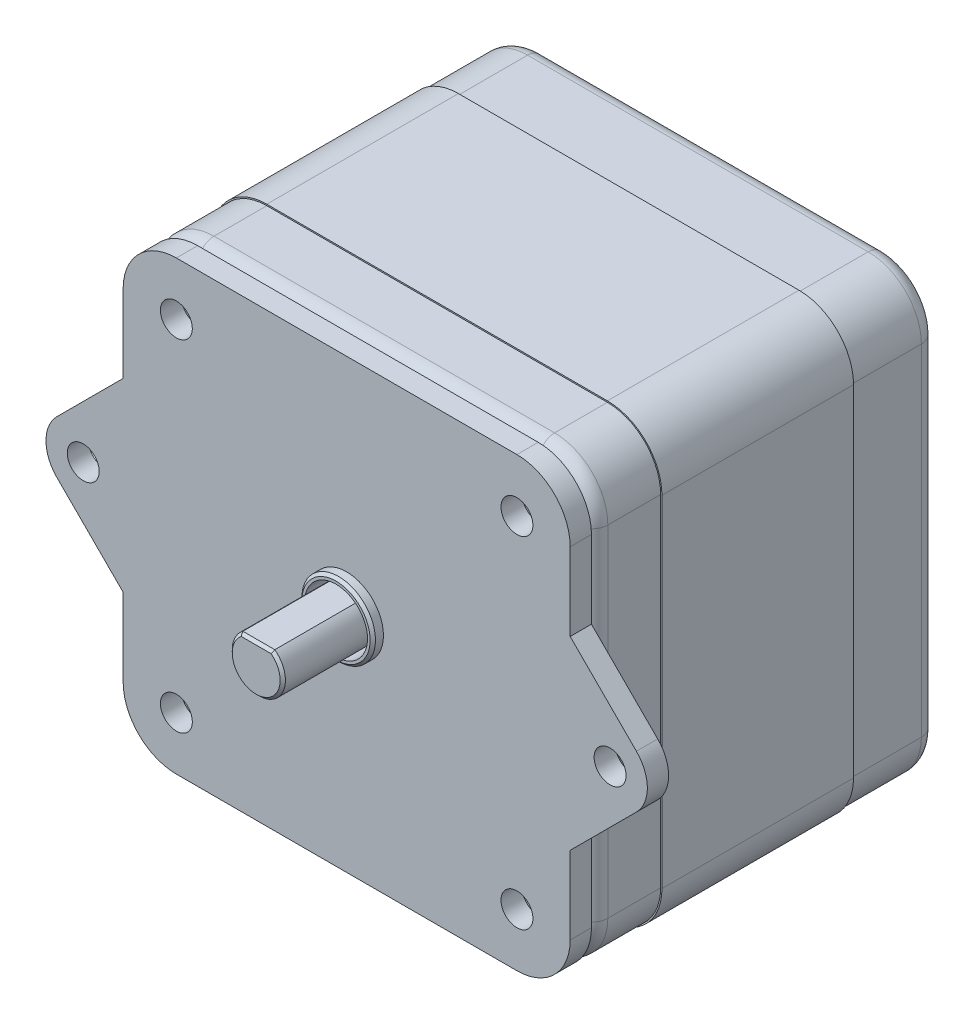
SolidWorks part; units mm, degrees
ref_plane "Front Plane" through (0, 0, 0) normal (0, 0, 1) x (1, 0, 0)
ref_plane "Top Plane" through (0, 0, 0) normal (0, 1, 0) x (1, 0, 0)
ref_plane "Right Plane" through (0, 0, 0) normal (1, 0, 0) x (0, 0, -1)
sketch "Sketch1" plane through (0, 0, 0) normal (0, 0, 1) x (1, 0, 0)
  line L0 (-27.2249, 2.4749) -> (-21, 8.6997)
  line L1 (-16, 21) -> (16, 21)
  line L2 (-21, 16) -> (-21, 8.6997)
  line L3 (-16, -21) -> (16, -21)
  line L4 (21, 16) -> (21, 8.6997)
  line L5 (-21, 21) -> (21, -21) construction
  line L6 (-21, -21) -> (21, 21) construction
  line L7 (-27.2249, -2.4749) -> (-21, -8.6997)
  line L8 (0, 14.4515) -> (0, -6.8676) construction
  line L9 (27.2249, -2.4749) -> (21, -8.6997)
  line L10 (27.2249, 2.4749) -> (21, 8.6997)
  line L11 (-21, -8.6997) -> (-21, -16)
  line L12 (21, -8.6997) -> (21, -16)
  arc A0 (-21, -16) -> (-16, -21) centre (-16, -16) ccw
  arc A1 (16, -21) -> (21, -16) centre (16, -16) ccw
  arc A2 (16, 21) -> (21, 16) centre (16, 16) cw
  arc A3 (-16, 21) -> (-21, 16) centre (-16, 16) ccw
  circle A4 centre (-24.75, 0) radius 1.5
  circle A5 centre (24.75, 0) radius 1.5
  arc A6 (27.2249, -2.4749) -> (27.2249, 2.4749) centre (24.75, 0) ccw
  arc A7 (-27.2249, 2.4749) -> (-27.2249, -2.4749) centre (-24.75, 0) ccw
  circle A8 centre (24.75, 0) radius 3.5 construction
  circle A9 centre (-24.75, 0) radius 3.5 construction
  point P0 (0, 0)
  dimension "D3" = 5
  dimension "D4" = 3
  dimension "D5" = 42
  dimension "D7" = 2
  dimension "D8" = 3
  dimension "D11" = 2
  dimension "D12" = 24.75
  dimension "D2" = 42
  dimension "D6" = 24.75
  dimension "D9" = 135
  dimension "D10" = 45
  dimension "D13" = 135
sketch "Sketch2" plane through (0, 0, 0) normal (0, 0, 1) x (1, 0, 0)
  line L0 (-21, 16) -> (-21, 8.6997) construction
  line L4 (-16, -21) -> (16, -21) construction
  line L8 (21, 16) -> (21, 8.6997) construction
  line L9 (-16, 21) -> (16, 21) construction
  line L10 (-21, 16) -> (-21, -16)
  line L14 (-16, -21) -> (16, -21)
  line L18 (21, 16) -> (21, -16)
  line L19 (-16, 21) -> (16, 21)
  arc A1 (-21, -16) -> (-16, -21) centre (-16, -16) ccw construction
  arc A2 (16, -21) -> (21, -16) centre (16, -16) ccw construction
  arc A4 (21, 16) -> (16, 21) centre (16, 16) ccw construction
  arc A5 (-16, 21) -> (-21, 16) centre (-16, 16) ccw construction
  arc A7 (-21, -16) -> (-16, -21) centre (-16, -16) ccw
  arc A8 (16, -21) -> (21, -16) centre (16, -16) ccw
  arc A10 (21, 16) -> (16, 21) centre (16, 16) ccw
  arc A11 (-16, 21) -> (-21, 16) centre (-16, 16) ccw
extrude "Boss-Extrude1" add sketch "Sketch2" against normal blind 34.5
sketch "Sketch3" plane through (0, 0, 0) normal (0, 0, 1) x (1, 0, 0)
  line L0 (-27.2249, 2.4749) -> (-21, 8.6997) construction
  line L1 (-21, 16) -> (-21, 8.6997) construction
  line L2 (-16, 21) -> (16, 21) construction
  line L3 (21, 16) -> (21, 8.6997) construction
  line L4 (27.2249, 2.4749) -> (21, 8.6997) construction
  line L5 (27.2249, -2.4749) -> (21, -8.6997) construction
  line L6 (21, -8.6997) -> (21, -16) construction
  line L7 (-16, -21) -> (16, -21) construction
  line L8 (-21, -8.6997) -> (-21, -16) construction
  line L9 (-27.2249, -2.4749) -> (-21, -8.6997) construction
  line L10 (-27.2249, 2.4749) -> (-21, 8.6997)
  line L11 (-21, 16) -> (-21, 8.6997)
  line L12 (-16, 21) -> (16, 21)
  line L13 (21, 16) -> (21, 8.6997)
  line L14 (27.2249, 2.4749) -> (21, 8.6997)
  line L15 (27.2249, -2.4749) -> (21, -8.6997)
  line L16 (21, -8.6997) -> (21, -16)
  line L17 (-16, -21) -> (16, -21)
  line L18 (-21, -8.6997) -> (-21, -16)
  line L19 (-27.2249, -2.4749) -> (-21, -8.6997)
  arc A0 (-16, 21) -> (-21, 16) centre (-16, 16) ccw construction
  arc A1 (21, 16) -> (16, 21) centre (16, 16) ccw construction
  arc A2 (27.2249, -2.4749) -> (27.2249, 2.4749) centre (24.75, 0) ccw construction
  arc A3 (16, -21) -> (21, -16) centre (16, -16) ccw construction
  arc A4 (-21, -16) -> (-16, -21) centre (-16, -16) ccw construction
  arc A5 (-27.2249, 2.4749) -> (-27.2249, -2.4749) centre (-24.75, 0) ccw construction
  circle A6 centre (-24.75, 0) radius 1.5 construction
  circle A7 centre (24.75, 0) radius 1.5 construction
  arc A8 (-16, 21) -> (-21, 16) centre (-16, 16) ccw
  arc A9 (21, 16) -> (16, 21) centre (16, 16) ccw
  arc A10 (27.2249, -2.4749) -> (27.2249, 2.4749) centre (24.75, 0) ccw
  arc A11 (16, -21) -> (21, -16) centre (16, -16) ccw
  arc A12 (-21, -16) -> (-16, -21) centre (-16, -16) ccw
  arc A13 (-27.2249, 2.4749) -> (-27.2249, -2.4749) centre (-24.75, 0) ccw
  circle A14 centre (-24.75, 0) radius 1.5
  circle A15 centre (24.75, 0) radius 1.5
extrude "Boss-Extrude2" add sketch "Sketch3" against normal blind 2
sketch "Sketch4" plane through (0, 0, 0) normal (0, 0, 1) x (1, 0, 0)
  line L0 (-1.5, 2) -> (1.5, 2)
  arc A0 (-1.5, 2) -> (1.5, 2) centre (0, 0) ccw
  dimension "D1" = 5
  dimension "D2" = 2
extrude "Boss-Extrude3" add sketch "Sketch4" along normal blind 8.5
sketch "Sketch5" plane through (0, 0, 0) normal (0, 0, 1) x (1, 0, 0)
  circle A0 centre (0, 0) radius 3.4575
  circle A1 centre (0, 0) radius 2.9575
  dimension "D1" = 0.5
extrude "Boss-Extrude4" add sketch "Sketch5" along normal blind 1
sketch "Sketch6" plane through (0, 0, 0) normal (0, 0, 1) x (1, 0, 0)
  line L1 (1.5, 2) -> (-1.5, 2)
  line L2 (1.5, 2) -> (-1.5, 2)
  circle A1 centre (0, 0) radius 2.9575
  circle A2 centre (0, 0) radius 2.9575
  arc A3 (-1.5, 2) -> (1.5, 2) centre (0, 0) ccw
  arc A4 (-1.5, 2) -> (1.5, 2) centre (0, 0) ccw
  dimension "D1" = 0
  dimension "D2" = 0
extrude "Cut-Extrude1" cut sketch "Sketch6" against normal blind 10
chamfer "Chamfer1" distance 0.25 angle 45 3 edges at (0, 2, 8.5) (0, -2.5, 8.5) (3.4575, 0, 1)
sketch "Sketch7" plane through (0, 0, -2) normal (0, 0, -1) x (-1, 0, 0)
  line L0 (-16, 21) -> (16, 21) construction
  line L1 (21, 16) -> (21, 8.6997) construction
  line L2 (-21, 8.6997) -> (-21, 16) construction
  line L3 (16, -21) -> (-16, -21) construction
  line L4 (-16, 21) -> (16, 21)
  line L5 (21, 16) -> (21, -16)
  line L6 (-21, -16) -> (-21, 16)
  line L7 (16, -21) -> (-16, -21)
  line L8 (-16, 20) -> (16, 20)
  line L9 (20, 16) -> (20, -16)
  line L10 (16, -20) -> (-16, -20)
  line L11 (-20, -16) -> (-20, 16)
  arc A0 (21, 16) -> (16, 21) centre (16, 16) ccw construction
  arc A1 (-16, 21) -> (-21, 16) centre (-16, 16) ccw construction
  arc A2 (-21, -16) -> (-16, -21) centre (-16, -16) ccw construction
  arc A3 (16, -21) -> (21, -16) centre (16, -16) ccw construction
  arc A4 (21, 16) -> (16, 21) centre (16, 16) ccw
  arc A5 (-16, 21) -> (-21, 16) centre (-16, 16) ccw
  arc A6 (-21, -16) -> (-16, -21) centre (-16, -16) ccw
  arc A7 (16, -21) -> (21, -16) centre (16, -16) ccw
  arc A8 (20, 16) -> (16, 20) centre (16, 16) ccw
  arc A9 (16, -20) -> (20, -16) centre (16, -16) ccw
  arc A10 (-20, -16) -> (-16, -20) centre (-16, -16) ccw
  arc A11 (-16, 20) -> (-20, 16) centre (-16, 16) ccw
  dimension "D1" = 1
extrude "Cut-Extrude2" cut sketch "Sketch7" along normal blind 0.125
fillet "Fillet1" radius 1.5 16 edges at (19.5355, 19.5355, -34.5) (21, 0, -34.5) (19.5355, -19.5355, -34.5) (0, -21, -34.5) (-19.5355, -19.5355, -34.5) (-21, 0, -34.5) (-19.5355, 19.5355, -34.5) (0, 21, -34.5) (-19.5355, 19.5355, -2.125) (-21, 0, -2.125) (-19.5355, -19.5355, -2.125) (0, -21, -2.125) (19.5355, -19.5355, -2.125) (21, 0, -2.125) (19.5355, 19.5355, -2.125) (0, 21, -2.125)
sketch "Sketch8" plane through (0, 0, 0) normal (0, 0, 1) x (1, 0, 0)
  line L0 (16, 21) -> (-16, 21) construction
  line L1 (-21, 16) -> (-21, 8.6997) construction
  line L2 (0, 8.3299) -> (0, 0) construction
  line L3 (0, 0) -> (7.0393, 0) construction
  circle A0 centre (-16, 16) radius 1.5
  circle A1 centre (16, 16) radius 1.5
  circle A2 centre (16, -16) radius 1.5
  circle A3 centre (-16, -16) radius 1.5
  dimension "D1" = 3
  dimension "D2" = 5
  dimension "D3" = 5
extrude "Cut-Extrude3" cut sketch "Sketch8" against normal up to vertex (2 mm away) up to point (-21, 8.6997, -2)
sketch "Sketch9" plane through (0, 0, -34.5) normal (0, 0, -1) x (-1, 0, 0)
  circle A0 centre (-16, 16) radius 1.5 construction
  circle A1 centre (16, 16) radius 1.5 construction
  circle A2 centre (16, -16) radius 1.5 construction
  circle A3 centre (-16, -16) radius 1.5 construction
  circle A4 centre (-16, 16) radius 1.5 construction
  circle A5 centre (16, 16) radius 1.5 construction
  circle A6 centre (16, -16) radius 1.5 construction
  circle A7 centre (-16, -16) radius 1.5 construction
  circle A8 centre (0, 0) radius 2.9575 construction
  circle A9 centre (0, 0) radius 2.9575
  circle A14 centre (-16, 16) radius 2.75
  circle A15 centre (16, 16) radius 2.75
  circle A16 centre (16, -16) radius 2.75
  circle A17 centre (-16, -16) radius 2.75
  dimension "D1" = 1.25
extrude "Boss-Extrude5" add sketch "Sketch9" along normal blind 0.5
sketch "Sketch10" plane through (0, 0, -35) normal (0, 0, -1) x (-1, 0, 0)
  line L0 (-17.5, 16) -> (-14.5, 16) construction
  line L1 (-16, 14.5) -> (-16, 17.5) construction
  line L2 (-15.5, 14.5) -> (-15.5, 15.5)
  line L3 (-17.5, 15.5) -> (-16.5, 15.5)
  line L4 (-16.5, 14.5) -> (-16.5, 15.5)
  line L5 (-17.5, 16.5) -> (-16.5, 16.5)
  line L6 (-16.5, 17.5) -> (-15.5, 17.5)
  line L7 (-14.5, 16.5) -> (-14.5, 15.5)
  line L8 (-15.5, 14.5) -> (-16.5, 14.5)
  line L9 (-17.5, 15.5) -> (-17.5, 16.5)
  line L10 (-15.5, 16.5) -> (-14.5, 16.5)
  line L11 (-17.5, 16.5) -> (-14.5, 16.5) construction
  line L12 (-16.5, 16.5) -> (-16.5, 17.5)
  line L13 (-16.5, 14.5) -> (-16.5, 17.5) construction
  line L14 (-15.5, 15.5) -> (-14.5, 15.5)
  line L15 (-17.5, 15.5) -> (-14.5, 15.5) construction
  line L16 (-15.5, 16.5) -> (-15.5, 17.5)
  line L17 (-15.5, 14.5) -> (-15.5, 17.5) construction
  line L18 (0, 5.9902) -> (0, 0) construction
  line L19 (0, 0) -> (6.6801, 0) construction
  line L20 (16, 14.5) -> (16, 17.5) construction
  line L21 (17.5, 16) -> (14.5, 16) construction
  line L22 (15.5, 16.5) -> (15.5, 17.5)
  line L23 (15.5, 15.5) -> (14.5, 15.5)
  line L24 (16.5, 16.5) -> (16.5, 17.5)
  line L25 (15.5, 16.5) -> (14.5, 16.5)
  line L26 (17.5, 15.5) -> (17.5, 16.5)
  line L27 (15.5, 14.5) -> (16.5, 14.5)
  line L28 (14.5, 16.5) -> (14.5, 15.5)
  line L29 (16.5, 17.5) -> (15.5, 17.5)
  line L30 (17.5, 16.5) -> (16.5, 16.5)
  line L31 (16.5, 14.5) -> (16.5, 15.5)
  line L32 (17.5, 15.5) -> (16.5, 15.5)
  line L33 (15.5, 14.5) -> (15.5, 15.5)
  line L34 (17.5, -16) -> (14.5, -16) construction
  line L35 (16, -14.5) -> (16, -17.5) construction
  line L36 (-16, -14.5) -> (-16, -17.5) construction
  line L37 (-17.5, -16) -> (-14.5, -16) construction
  line L38 (15.5, -14.5) -> (15.5, -15.5)
  line L39 (17.5, -15.5) -> (16.5, -15.5)
  line L40 (16.5, -14.5) -> (16.5, -15.5)
  line L41 (17.5, -16.5) -> (16.5, -16.5)
  line L42 (16.5, -17.5) -> (15.5, -17.5)
  line L43 (14.5, -16.5) -> (14.5, -15.5)
  line L44 (15.5, -14.5) -> (16.5, -14.5)
  line L45 (17.5, -15.5) -> (17.5, -16.5)
  line L46 (15.5, -16.5) -> (14.5, -16.5)
  line L47 (16.5, -16.5) -> (16.5, -17.5)
  line L48 (15.5, -15.5) -> (14.5, -15.5)
  line L49 (15.5, -16.5) -> (15.5, -17.5)
  line L50 (-15.5, -16.5) -> (-15.5, -17.5)
  line L51 (-15.5, -15.5) -> (-14.5, -15.5)
  line L52 (-16.5, -16.5) -> (-16.5, -17.5)
  line L53 (-15.5, -16.5) -> (-14.5, -16.5)
  line L54 (-17.5, -15.5) -> (-17.5, -16.5)
  line L55 (-15.5, -14.5) -> (-16.5, -14.5)
  line L56 (-14.5, -16.5) -> (-14.5, -15.5)
  line L57 (-16.5, -17.5) -> (-15.5, -17.5)
  line L58 (-17.5, -16.5) -> (-16.5, -16.5)
  line L59 (-16.5, -14.5) -> (-16.5, -15.5)
  line L60 (-17.5, -15.5) -> (-16.5, -15.5)
  line L61 (-15.5, -14.5) -> (-15.5, -15.5)
  point P6 (-16, 16)
  point P38 (16, 16)
  point P71 (16, -16)
  point P72 (-16, -16)
  dimension "D1" = 1.5
  dimension "D2" = 1.5
  dimension "D3" = 0.5
  dimension "D4" = 0.5
extrude "Cut-Extrude4" cut sketch "Sketch10" against normal blind 1
ref_plane "Plane1" through (0, 0, -26.5) normal (0, 0, -1) x (-1, 0, 0)
sketch "Sketch11" plane through (0, 0, -26.5) normal (0, 0, -1) x (-1, 0, 0)
  line L0 (-16, 21) -> (16, 21) construction
  line L1 (-21, -16) -> (-21, 16) construction
  line L2 (21, 16) -> (21, -16) construction
  line L3 (16, -21) -> (-16, -21) construction
  line L4 (-16, 21) -> (16, 21)
  line L5 (-21, -16) -> (-21, 16)
  line L6 (21, 16) -> (21, -16)
  line L7 (16, -21) -> (-16, -21)
  line L8 (-21.125, -16) -> (-21.125, 16)
  line L9 (16, -21.125) -> (-16, -21.125)
  line L10 (21.125, 16) -> (21.125, -16)
  line L11 (-16, 21.125) -> (16, 21.125)
  arc A0 (-16, 21) -> (-21, 16) centre (-16, 16) ccw construction
  arc A1 (21, 16) -> (16, 21) centre (16, 16) ccw construction
  arc A2 (16, -21) -> (21, -16) centre (16, -16) ccw construction
  arc A3 (-21, -16) -> (-16, -21) centre (-16, -16) ccw construction
  arc A4 (-16, 21) -> (-21, 16) centre (-16, 16) ccw
  arc A5 (21, 16) -> (16, 21) centre (16, 16) ccw
  arc A6 (16, -21) -> (21, -16) centre (16, -16) ccw
  arc A7 (-21, -16) -> (-16, -21) centre (-16, -16) ccw
  arc A8 (-16, 21.125) -> (-21.125, 16) centre (-16, 16) ccw
  arc A9 (-21.125, -16) -> (-16, -21.125) centre (-16, -16) ccw
  arc A10 (16, -21.125) -> (21.125, -16) centre (16, -16) ccw
  arc A11 (21.125, 16) -> (16, 21.125) centre (16, 16) ccw
  dimension "D1" = 0.125
extrude "Boss-Extrude6" add sketch "Sketch11" against normal blind 18
